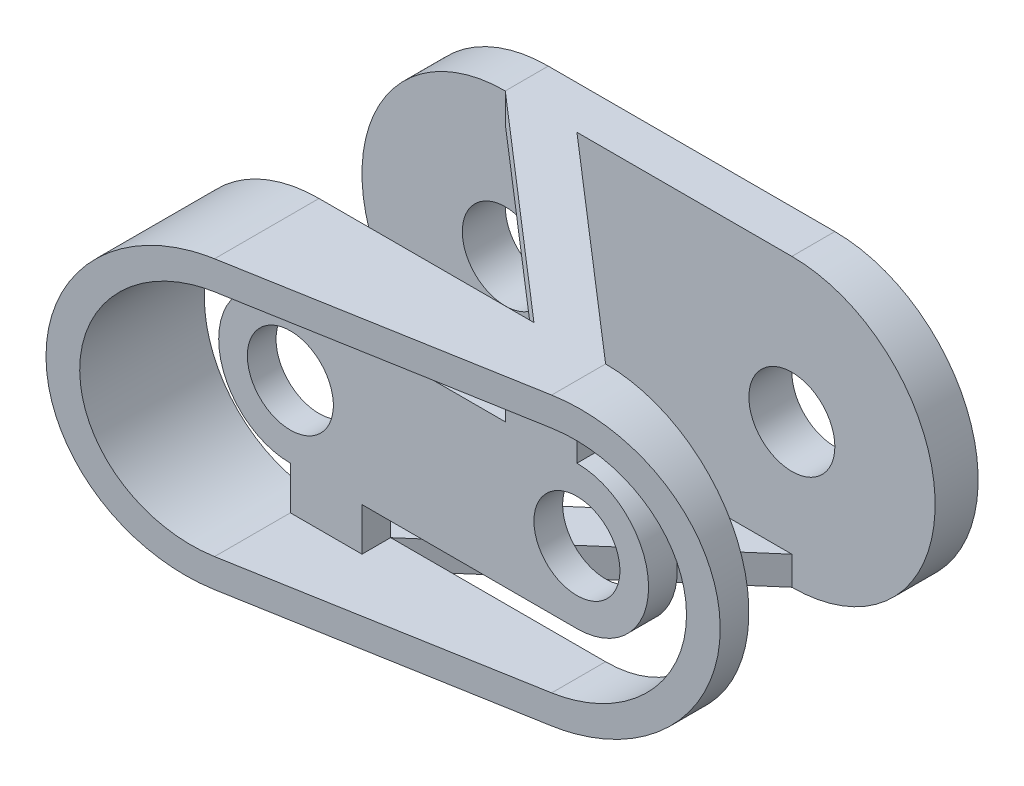
SolidWorks part; units mm, degrees
ref_plane "Front Plane" through (0, 0, 0) normal (0, 0, 1) x (1, 0, 0)
ref_plane "Top Plane" through (0, 0, 0) normal (0, 1, 0) x (1, 0, 0)
ref_plane "Right Plane" through (0, 0, 0) normal (1, 0, 0) x (0, 0, -1)
sketch "Sketch1" plane through (0, 0, 0) normal (0, 0, 1) x (1, 0, 0)
  line L1 (50, -50) -> (-50, -50)
  line L3 (50, 50) -> (-50, 50)
  arc A0 (50, -50) -> (50, 50) centre (50, 0) ccw
  arc A1 (-50, 50) -> (-50, -50) centre (-50, 0) ccw
  circle A2 centre (-50, 0) radius 15
  circle A3 centre (50, 0) radius 15
  point P0 (0, 0)
  dimension "D3" = 30
  dimension "D1" = 100
  dimension "D2" = 100
extrude "Boss-Extrude1" add sketch "Sketch1" along normal blind 15
extrude "Boss-Extrude2" add sketch "Sketch1<3>" along normal blind 70 from offset 80 separate body contours L1 A1 L3 A0
sketch "Sketch1<3>" plane through (0, 0, 0) normal (0, 0, 1) x (1, 0, 0) same geometry as "Sketch1"
sketch "Sketch3" plane through (0, 0, 0) normal (0, 1, 0) x (1, 0, 0)
  line L0 (100, -90) -> (-100, -125.2654)
  line L1 (100, -150) -> (100, -80) construction
  line L2 (-100, -80) -> (-100, -150) construction
  line L7 (-100, -125.2654) -> (-100, -150)
  line L8 (-100, -150) -> (100, -150)
  line L9 (100, -150) -> (100, -90)
extrude "Cut-Extrude1" cut sketch "Sketch3" against normal through all both and the other way through all
sketch "Sketch4" plane through (0, 0, 80) normal (0, 0, -1) x (-1, 0, 0)
  line L1 (-50, -25) -> (25, -25)
  line L3 (-25, 25) -> (50, 25)
  line L20 (-50, 25) -> (-50, 40)
  line L21 (-50, 40) -> (-25, 40)
  line L22 (-25, 40) -> (-25, 25)
  line L23 (25, -25) -> (25, -40)
  line L24 (25, -40) -> (50, -40)
  line L25 (50, -40) -> (50, -25)
  arc A0 (50, -25) -> (50, 25) centre (50, 0) ccw
  arc A1 (-50, 25) -> (-50, -25) centre (-50, 0) ccw
  circle A2 centre (-50, 0) radius 15
  circle A3 centre (50, 0) radius 15
  point P0 (0, 0)
  point P22 (0, 0)
  dimension "D5" = 30
  dimension "D1" = 100
  dimension "D2" = 50
  dimension "D7" = 15
  dimension "D8" = 15
extrude "Cut-Extrude2" cut sketch "Sketch4" against normal blind 70 contours A2 | A2 | A3 | A3 region at (50, 0, 80) region at (-50, 0, 80)
sketch "Sketch6" plane through (0, 0, 80) normal (0, 0, -1) x (-1, 0, 0)
  line L1 (50, -40) -> (-50, -40)
  line L3 (50, 40) -> (-50, 40)
  arc A0 (-50, 40) -> (-50, -40) centre (-50, 0) ccw
  arc A1 (50, -40) -> (50, 40) centre (50, 0) ccw
  point P0 (0, 0)
  dimension "D1" = 100
  dimension "D2" = 80
extrude "Cut-Extrude4" cut sketch "Sketch6" against normal blind 70
extrude "Boss-Extrude4" add sketch "Sketch4<4>" against normal blind 10
sketch "Sketch4<4>" plane through (0, 0, 80) normal (0, 0, -1) x (-1, 0, 0) same geometry as "Sketch4"
sketch "Sketch8" plane through (0, -50, 0) normal (0, -1, 0) x (1, 0, 0)
  line L0 (-50, 80) -> (-25, 80)
  line L2 (-25, 80) -> (50, 15)
  line L3 (50, 15) -> (25, 15)
  line L4 (-50, 15) -> (50, 15) construction
  line L5 (-50, 80) -> (25, 15)
  dimension "D1" = 25
extrude "Boss-Extrude5" add sketch "Sketch8" against normal blind 10
sketch "Sketch9" plane through (0, 50, 0) normal (0, 1, 0) x (1, 0, 0)
  line L0 (50, -80) -> (25, -80)
  line L1 (-50, -15) -> (-25, -15)
  line L2 (50, -15) -> (-50, -15) construction
  line L3 (-50, -15) -> (25, -80)
  line L4 (50, -80) -> (-25, -15)
  dimension "D1" = 25
extrude "Boss-Extrude6" add sketch "Sketch9" against normal blind 10
